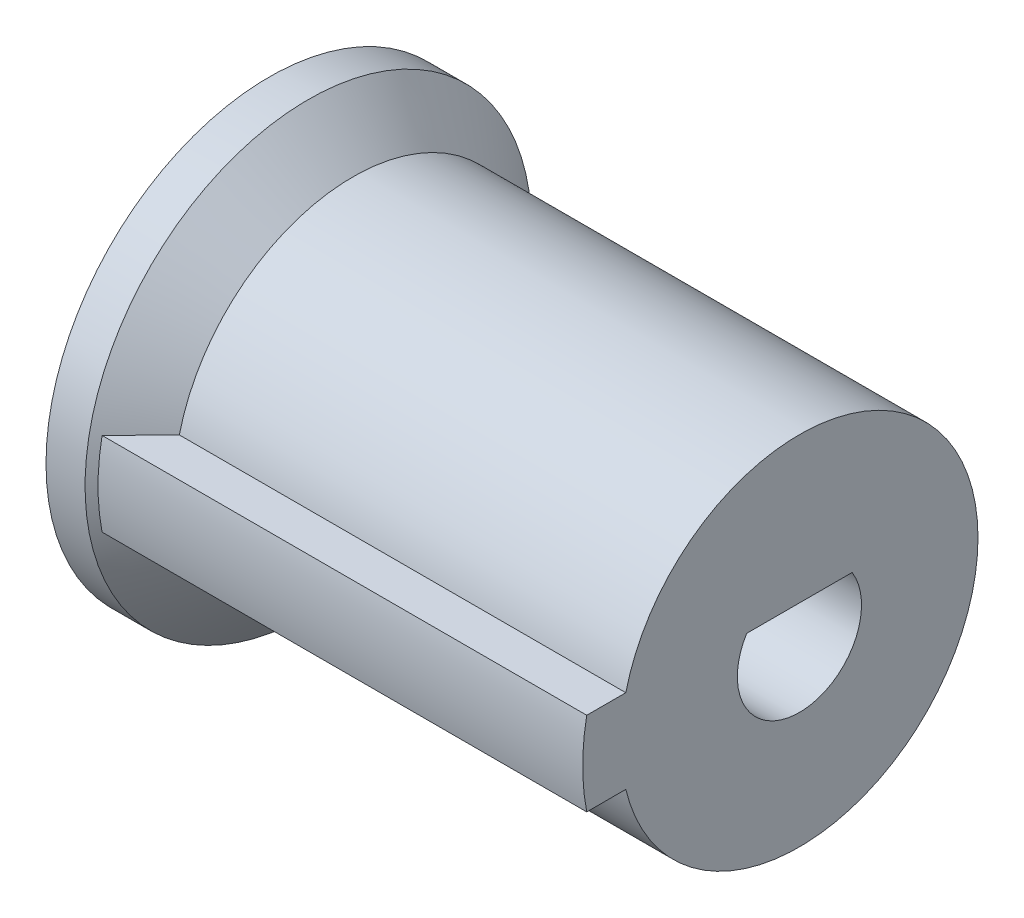
SolidWorks part; units mm, degrees
ref_plane "Alzado" through (0, 0, 0) normal (0, 0, 1) x (1, 0, 0)
ref_plane "Planta" through (0, 0, 0) normal (0, 1, 0) x (1, 0, 0)
ref_plane "Vista lateral" through (0, 0, 0) normal (1, 0, 0) x (0, 0, -1)
sketch "Croquis1" plane through (0, 0, 0) normal (1, 0, 0) x (0, 0, -1)
  line L0 (-1.8894, 1.175) -> (1.8894, 1.175)
  line L1 (0, -2.225) -> (3.8969, -2.225) construction
  line L2 (-9.3844, 0) -> (9.3844, 0) construction
  line L3 (-6.2217, 1.5) -> (-7.6217, 1.5)
  line L4 (-6.2217, -1.5) -> (-7.6217, -1.5)
  circle A0 centre (0, 0) radius 2.225
  circle A1 centre (0, 0) radius 8
  circle A2 centre (0, 0) radius 6.4
  arc A3 (-7.6217, 1.5) -> (-7.6217, -1.5) centre (0, 0) ccw
  point P12 (0, 0)
  dimension "D1" = 4.45
  dimension "D3" = 12.8
  dimension "D4" = 16
  dimension "D2" = 3.4
  dimension "D5" = 1.4
  dimension "D6" = 1.5
extrude "Saliente-Extruir1" add sketch "Croquis1" along normal blind 16 contours L3 A3 L4 A2 | A2 A0 | L0 A0 region at (0, 1.6049, 0) region at (0, 0, 7.0298) region at (0, 6.1755, -0.7339)
extrude "Saliente-Extruir3" add sketch "Croquis1<4>" against normal blind 3 contours A1 A3 L3 A2 L4 | A2 A0 | L3 A3 L4 A2 | L0 A0 region at (0, 1.6049, 0) region at (0, 0, 7.0298) region at (0, 6.1755, -0.7339) region at (0, 0, 7.7737)
sketch "Croquis1<4>" plane through (0, 0, 0) normal (1, 0, 0) x (0, 0, -1) same geometry as "Croquis1"
chamfer "Chaflán2" distance 1.6 angle 45 1 edges at (0, 0, -8)
